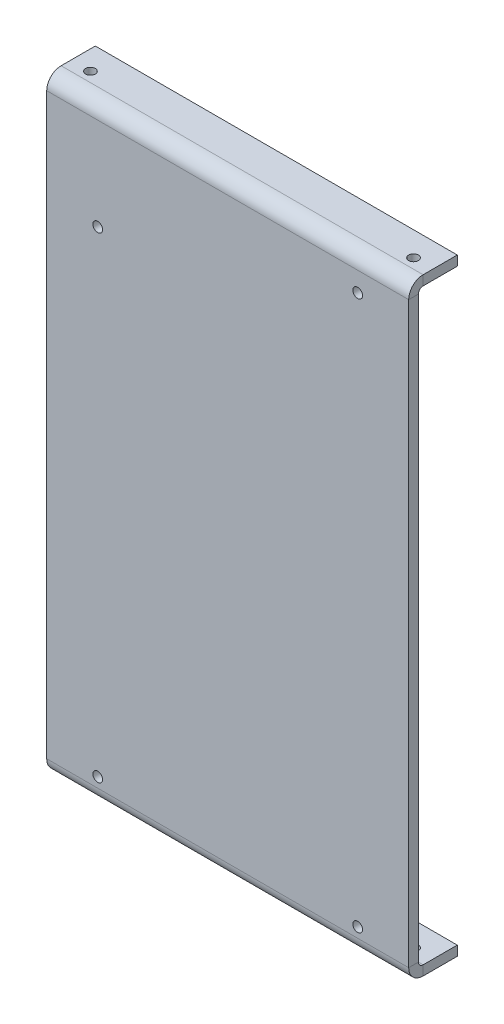
SolidWorks part; units mm, degrees
note: The reader was unsure of these and kept them because the rebuilt part matched: flange length of "Edge-Flange2".
ref_plane "Front Plane" through (0, 0, 0) normal (1, 0, 0) x (0, 1, 0)
ref_plane "Top Plane" through (0, 0, 0) normal (0, 0, 1) x (0, 1, 0)
ref_plane "Right Plane" through (0, 0, 0) normal (0, 1, 0) x (-1, 0, 0)
sketch "Sketch1" plane through (0, 0, 0) normal (0, 0, 1) x (0, 1, 0)
  line L1 (-116.5, 57) -> (3.5, 57) construction
  line L2 (-116.5, 57) -> (-116.5, -3.5) construction
  line L3 (-116.5, -3.5) -> (3.5, -3.5) construction
  line L4 (3.5, 57) -> (3.5, -3.5) construction
  line L9 (-118, 64) -> (7, 64)
  line L10 (-118, 64) -> (-118, -10.5)
  line L11 (-118, -10.5) -> (7, -10.5)
  line L12 (7, 64) -> (7, -10.5)
  circle A0 centre (0, 0) radius 1
  circle A1 centre (-113, 0) radius 1
  circle A2 centre (-113, 53.5) radius 1
  circle A3 centre (-15, 53.5) radius 1
  point P9 (0, 0)
  point P25 (0, 0)
  point P26 (0, 0)
  point P27 (0, 0)
  point P28 (0, 0)
  dimension "D1" = 2
  dimension "D9" = 1.5
  dimension "D2" = 113
  dimension "D3" = 53.5
  dimension "D4" = 98
  dimension "D5" = 3.5
  dimension "D6" = 3.5
  dimension "D7" = 3.5
  dimension "D8" = 3.5
  dimension "D13" = 125
  dimension "D14" = 7
  dimension "D19" = 7
base flange "Base-Flange1" sketch "Sketch1" thickness 2 reverse thickness direction no parameters "D1"=0.9652
edge flange "Edge-Flange2" sketch "Sketch18" flange profiles "Sketch18", "Sketch19" flange angle 90 flange length 10 flange position material inside bend radius 0.9652 thickness 2 relief rectangular parameters "D6"=10, "D8"=1
sketch "Sketch18" plane through (0, -118, -2) normal (0, -1, 0) x (-1, 0, 0)
  line L0 (64, 0) -> (-10.5, 0) construction
  line L1 (64, 0) -> (-10.5, 0)
  line L2 (-10.5, 0) -> (-10.5, 8)
  line L3 (-10.5, 8) -> (64, 8)
  line L4 (64, 8) -> (64, 0)
sketch "Sketch19" plane through (0, 7, -2) normal (0, 1, 0) x (1, 0, 0)
  line L0 (10.5, 0) -> (-64, 0) construction
  line L1 (10.5, 0) -> (-64, 0)
  line L2 (10.5, 0) -> (10.5, 8)
  line L3 (10.5, 8) -> (-64, 8)
  line L4 (-64, 8) -> (-64, 0)
bend "EdgeBend3" bend radius 0.9652 bend angle 90 parameters "D5"=1
bend "EdgeBend4" bend radius 0.9652 bend angle 90 parameters "D5"=2
sketch "Sketch20" plane through (0, -118, 0) normal (0, -1, 0) x (1, 0, 0)
  line L0 (-64, -2.9652) -> (-64, -10) construction
  line L1 (10.5, -10) -> (10.5, -2.9652) construction
  line L2 (-64, 0) -> (10.5, 0) construction
  circle A0 centre (-60, -5) radius 1
  circle A1 centre (6.5, -5) radius 1
  point P4 (0, 0)
  dimension "D1" = 2
  dimension "D2" = 4
  dimension "D3" = 4
  dimension "D4" = 66.5
  dimension "D5" = 5
extrude "Cut-Extrude2" cut sketch "Sketch20" against normal through all normal cut yes
sketch "Bend-Lines1" [suppressed] plane through (0, 0, 0) normal (0, 1, 0) x (-1, 0, 0)
sketch "Bounding-Box1" [suppressed] plane through (0, 0, 0) normal (0, 1, 0) x (-1, 0, 0)
sheet metal parameters "Sheet-Metal16" thickness 2 parameters "D1"=0.9652
flat pattern "Flat-Pattern16" [suppressed]
sketch "Bend-Lines2" plane through (0, 0, 0) normal (0, 1, 0) x (-1, 0, 0)
sketch "Bounding-Box2" [suppressed] plane through (0, 0, 0) normal (0, 1, 0) x (-1, 0, 0)
sheet metal parameters "Sheet-Metal18" thickness 2 parameters "D1"=0.9652
flat pattern "Flat-Pattern16" [suppressed]
sketch "Bend-Lines2" plane through (0, 0, 0) normal (0, 1, 0) x (-1, 0, 0)
sketch "Bounding-Box2" [suppressed] plane through (0, 0, 0) normal (0, 1, 0) x (-1, 0, 0)
bend of the flat pattern "Flatten-<EdgeBend3>1"
bend of the flat pattern "Flatten-<EdgeBend4>1"
sheet metal parameters "Sheet-Metal19" thickness 2 parameters "D1"=0.9652
flat pattern "Flat-Pattern16"
sketch "Bend-Lines2" plane through (0, 0, 0) normal (0, 0, 1) x (1, 0, 0)
  line L0 (10.5, 5.5783) -> (-64, 5.5783) construction
  line L1 (-64, -116.5783) -> (10.5, -116.5783) construction
  line L2 (10.5, 5.5783) -> (-64, 5.5783) construction
  line L3 (-64, -116.5783) -> (10.5, -116.5783) construction
sketch3d "Bounding-Box2" [suppressed]
  line L0 (10.5, 14.1565, 0) -> (10.5, -125.1565, 0) construction
  line L1 (-64, 14.1565, 0) -> (-64, -125.1565, 0) construction
  line L2 (10.5, 14.1565, 0) -> (-64, 14.1565, 0) construction
  line L3 (10.5, -125.1565, 0) -> (-64, -125.1565, 0) construction
bend of the flat pattern "Flatten-<EdgeBend3>1"
bend of the flat pattern "Flatten-<EdgeBend4>1"
